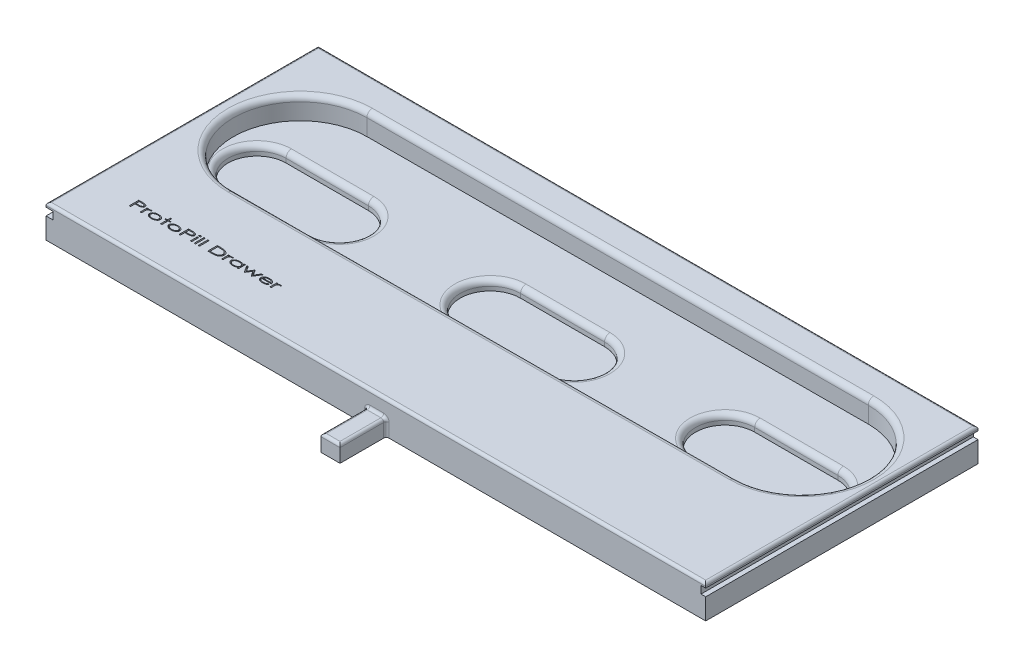
SolidWorks part; units mm, degrees
ref_plane "Front Plane" through (0, 0, 0) normal (0, 0, 1) x (1, 0, 0)
ref_plane "Top Plane" through (0, 0, 0) normal (0, 1, 0) x (1, 0, 0)
ref_plane "Right Plane" through (0, 0, 0) normal (1, 0, 0) x (0, 0, -1)
sketch "Sketch1" plane through (0, 0, 0) normal (0, 1, 0) x (1, 0, 0)
  line L2 (2.2154, -28.3198) -> (244.3174, -28.3198)
  line L4 (244.3174, 64.6802) -> (2.2154, 64.6802)
  line L6 (244.3174, 64.6802) -> (244.3174, -28.3198)
  line L7 (2.2154, 64.6802) -> (2.2154, -28.3198)
  dimension "D2" = 93
extrude "Boss-Extrude1" add sketch "Sketch1" along normal blind 12
sketch "Sketch3" plane through (0, 12, 0) normal (0, 1, 0) x (1, 0, 0)
  line L0 (37.1381, -19.9605) -> (-7.858, -19.9605) construction
  line L2 (37.1381, -19.9605) -> (37.1381, -24.4605) construction
  line L4 (37.1381, -19.9605) -> (123.1941, -19.9579) construction
  line L5 (123.6473, -19.9605) -> (210.1566, -19.9605) construction
  line L6 (210.1566, -19.9605) -> (210.1566, -24.4605) construction
  line L7 (123.6473, -19.9605) -> (123.6473, -24.4605) construction
  line L8 (37.1381, -19.9605) -> (37.1381, 7.1502) construction
  line L9 (123.6473, -19.9605) -> (123.6473, 8.5509) construction
  line L10 (210.1566, -19.9605) -> (210.1566, 7.8884) construction
  line L11 (0.0174, -19.9605) -> (247.1649, -19.9605)
  circle A2 centre (123.7727, -8.9393) radius 11.15
  circle A3 centre (37.3245, -8.6421) radius 11.15
  circle A4 centre (209.8985, -8.6813) radius 11.15
  dimension "D2" = 22.3
  dimension "D3" = 22.3
  dimension "D4" = 22.3
sketch "Sketch2" plane through (0, 0, 28.3198) normal (0, 0, 1) x (1, 0, 0)
  line L0 (0, 10.4529) -> (0, 7.6902)
  line L2 (0, 7.6902) -> (4.6941, 7.6902)
  line L3 (4.6941, 7.6902) -> (4.6941, 10.4529)
  line L5 (4.6941, 10.4529) -> (0, 10.4529)
extrude "Cut-Extrude1" cut sketch "Sketch2" against normal through all
ref_plane "Plane1" through (123.6473, 0, 0) normal (1, 0, 0) x (0, 0, -1)
mirror "Mirror5" about plane through (123.6473, 0, 0) normal (1, 0, 0) of "Cut-Extrude1"
sketch "Sketch7" plane through (0, 0, 28.3198) normal (0, 0, 1) x (1, 0, 0)
  line L0 (123.5912, 12) -> (123.6473, 0) construction
  line L1 (0.0174, 12) -> (247.1649, 12) construction
  line L2 (2.2154, 0) -> (244.3174, 0) construction
  line L3 (123.6473, -6.6) -> (123.6473, 6.6) construction
  line L9 (120.1263, 5.9887) -> (129.5137, 6.0191) construction
  line L10 (117.7248, 6.0191) -> (127.1122, 5.9887) construction
  line L11 (120.1263, 0) -> (127.1122, 0)
  line L12 (120.1263, 0) -> (120.1263, 5.9887)
  line L13 (120.1263, 5.9887) -> (127.1122, 5.9887)
  line L14 (127.1122, 0) -> (127.1122, 5.9887)
  point P8 (123.6193, 6)
extrude "Boss-Extrude2" add sketch "Sketch7" along normal blind 70
sketch "Sketch8" plane through (0, 0, 28.3198) normal (0, 0, 1) x (1, 0, 0)
  line L10 (244.3174, 10.4529) -> (244.3174, 12)
  line L12 (244.3174, 10.4529) -> (244.3174, 12)
  line L14 (244.3174, 12) -> (2.2154, 12)
  line L18 (2.2154, 12) -> (2.2154, 10.4529)
  line L19 (2.2154, 10.4529) -> (4.6941, 10.4529)
  line L20 (4.6941, 10.4529) -> (4.6941, 7.6902)
  line L21 (4.6941, 7.6902) -> (2.2154, 7.6902)
  line L22 (2.2154, 7.6902) -> (2.2154, 0)
  line L23 (2.2154, 0) -> (120.1263, 0)
  line L24 (120.1263, 0) -> (120.1263, 5.9887)
  line L30 (120.1263, 5.9887) -> (127.1122, 5.9887)
  line L31 (120.1263, 5.9887) -> (127.1122, 5.9887)
  line L34 (2.2154, 12) -> (2.2154, 10.4529)
  line L35 (2.2154, 10.4529) -> (4.6941, 10.4529)
  line L36 (4.6941, 10.4529) -> (4.6941, 7.6902)
  line L37 (4.6941, 7.6902) -> (2.2154, 7.6902)
  line L38 (2.2154, 7.6902) -> (2.2154, 0)
  line L39 (2.2154, 0) -> (120.1263, 0)
  line L40 (120.1263, 0) -> (120.1263, 5.9887)
  line L48 (127.1122, 5.9887) -> (127.1122, 0)
  line L49 (127.1122, 5.9887) -> (127.1122, 0)
  line L50 (127.1122, 0) -> (244.3174, 0)
  line L51 (127.1122, 0) -> (244.3174, 0)
  line L52 (244.3174, 0) -> (244.3174, 7.6902)
  line L53 (244.3174, 0) -> (244.3174, 7.6902)
  line L54 (244.3174, 7.6902) -> (242.6006, 7.6902)
  line L55 (244.3174, 7.6902) -> (242.6006, 7.6902)
  line L56 (242.6006, 7.6902) -> (242.6006, 10.4529)
  line L57 (242.6006, 7.6902) -> (242.6006, 10.4529)
  line L58 (242.6006, 10.4529) -> (244.3174, 10.4529)
  line L59 (242.6006, 10.4529) -> (244.3174, 10.4529)
  line L60 (244.3174, 12) -> (2.2154, 12)
  dimension "D1" = 0
extrude "Boss-Extrude3" add sketch "Sketch8" along normal blind 53
sketch "Sketch9" plane through (0, 12, 0) normal (0, 1, 0) x (1, 0, 0)
  line L0 (32.277, -18.0846) -> (215.6701, -17.457) construction
  line L3 (32.193, 6.4621) -> (215.5861, 7.0898)
  line L4 (32.361, -42.6314) -> (215.7541, -42.0037)
  arc A0 (32.193, 6.4621) -> (32.361, -42.6314) centre (32.277, -18.0846) ccw
  arc A1 (215.7541, -42.0037) -> (215.5861, 7.0898) centre (215.6701, -17.457) ccw
  point P6 (123.9735, -17.7708)
extrude "Cut-Extrude2" cut sketch "Sketch9" against normal blind 8
sketch "Sketch10" plane through (0, 4, 0) normal (0, 1, 0) x (1, 0, 0)
  line L0 (22.2559, -23.9029) -> (52.4711, -23.9029) construction
  line L1 (22.2559, -13.2713) -> (52.4711, -13.2713)
  line L2 (22.2559, -34.5345) -> (52.4711, -34.5345)
  line L3 (108.2536, -24.2865) -> (139.0697, -24.2865) construction
  line L4 (108.2536, -13.2003) -> (139.0697, -13.2003)
  line L5 (108.2536, -35.3728) -> (139.0697, -35.3728)
  line L6 (193.8044, -23.6865) -> (224.3383, -23.6865) construction
  line L7 (193.8044, -12.8155) -> (224.3383, -12.8155)
  line L8 (193.8044, -34.5575) -> (224.3383, -34.5575)
  arc A0 (22.2559, -13.2713) -> (22.2559, -34.5345) centre (22.2559, -23.9029) ccw
  arc A1 (52.4711, -34.5345) -> (52.4711, -13.2713) centre (52.4711, -23.9029) ccw
  arc A2 (108.2536, -13.2003) -> (108.2536, -35.3728) centre (108.2536, -24.2865) ccw
  arc A3 (139.0697, -35.3728) -> (139.0697, -13.2003) centre (139.0697, -24.2865) ccw
  arc A4 (193.8044, -12.8155) -> (193.8044, -34.5575) centre (193.8044, -23.6865) ccw
  arc A5 (224.3383, -34.5575) -> (224.3383, -12.8155) centre (224.3383, -23.6865) ccw
  point P2 (37.3635, -23.9029)
  point P9 (123.6616, -24.2865)
  point P16 (209.0714, -23.6865)
extrude "Cut-Extrude4" cut sketch "Sketch10" against normal blind 3.5
fillet "Fillet2" radius 2 4 edges at (240.2169, 12, 17.373) (124.0576, 12, 42.3176) (7.7302, 12, 18.1686) (123.8895, 12, -6.776)
fillet "Fillet3" radius 2 12 edges at (235.2093, 4, 23.6865) (209.0714, 4, 34.5575) (182.9335, 4, 23.6865) (150.1559, 4, 24.2865) (123.6616, 4, 35.3728) (97.1674, 4, 24.2865) (63.1027, 4, 23.9029) (37.3635, 4, 34.5345) (11.6243, 4, 23.9029) (209.0714, 4, 12.8155) (123.6616, 4, 13.2003) (37.3635, 4, 13.2713)
sketch "Sketch11" plane through (0, 12, 0) normal (0, 1, 0) x (1, 0, 0)
  line L0 (2.2154, 18.6064) -> (244.3174, 18.6064)
  line L1 (2.2154, 64.6802) -> (2.2154, -81.3198) construction
  line L2 (244.3174, -81.3198) -> (244.3174, 64.6802) construction
  line L3 (244.3174, 18.6064) -> (244.3174, 64.6802)
  line L4 (244.3174, 64.6802) -> (2.2154, 64.6802)
  line L5 (2.2154, 64.6802) -> (2.2154, 18.6064)
extrude "Cut-Extrude5" cut sketch "Sketch11" against normal through all
fillet "Fillet4" radius 1 10 edges at (120.1263, 2.9943, 81.3198) (127.1122, 2.9943, 81.3198) (123.6193, 5.9887, 98.3198) (120.1263, 5.9887, 89.8198) (123.6193, 5.9887, 81.3198) (127.1122, 5.9887, 89.8198) (244.3174, 12, 31.3567) (123.2664, 12, 81.3198) (2.2154, 12, 31.3567) (123.2664, 12, -18.6064)
sketch "Sketch12" plane through (0, 0, 0) normal (0, -1, 0) x (1, 0, 0)
  circle A0 centre (79.2049, -2.6546) radius 3.025
  circle A2 centre (79.2049, 6.3419) radius 3.025
  circle A10 centre (169.8585, 5.9307) radius 3.025
  circle A11 centre (169.8585, -2.6546) radius 3.025
extrude "Cut-Extrude6" cut sketch "Sketch12" against normal blind 2
sketch "Sketch13" plane through (0, 12, 0) normal (0, 1, 0) x (1, 0, 0)
  text T0 "ProtoPill Drawer" font "Century Gothic" height 3.5
extrude "Cut-Extrude7" cut sketch "Sketch13" against normal blind 2
sketch "Sketch14" plane through (0, 0, 0) normal (0, -1, 0) x (1, 0, 0)
  line L0 (76.1475, 6.1393) -> (79.1725, 12.8178)
  line L1 (79.1725, 12.8178) -> (82.1975, 6.1393)
  line L2 (82.1975, 6.1393) -> (76.1475, 6.1393)
  line L3 (76.1475, -2.8572) -> (79.1725, -9.5356)
  line L4 (79.1725, -9.5356) -> (82.1975, -2.8572)
  line L5 (82.1975, -2.8572) -> (76.1475, -2.8572)
  line L6 (166.8011, 5.7281) -> (169.8261, 12.4066)
  line L7 (169.8261, 12.4066) -> (172.8511, 5.7281)
  line L8 (172.8511, 5.7281) -> (166.8011, 5.7281)
  line L9 (166.8011, -2.8572) -> (169.8261, -9.5356)
  line L10 (169.8261, -9.5356) -> (172.8511, -2.8572)
  line L11 (172.8511, -2.8572) -> (166.8011, -2.8572)
extrude "Cut-Extrude8" cut sketch "Sketch14" against normal blind 2
sketch "Sketch15" plane through (0, 12, 0) normal (0, 1, 0) x (1, 0, 0)
  line L2 (146.7092, -47.8489) -> (134.6091, -54.4141)
  line L3 (146.7092, -47.8489) -> (146.7092, -74.4208)
  line L4 (146.7092, -74.4208) -> (134.6091, -67.8555)
